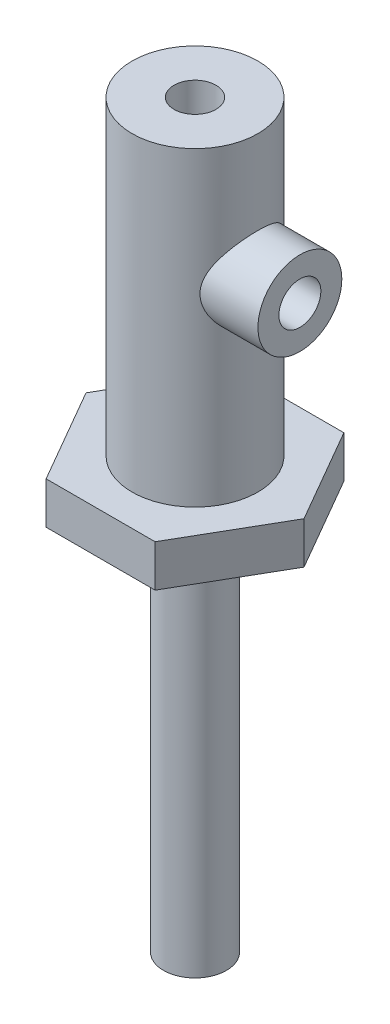
SolidWorks part; units mm, degrees
ref_plane "Front Plane" through (0, 0, 0) normal (0, 0, 1) x (1, 0, 0)
ref_plane "Top Plane" through (0, 0, 0) normal (0, 1, 0) x (1, 0, 0)
ref_plane "Right Plane" through (0, 0, 0) normal (1, 0, 0) x (0, 0, -1)
sketch "Sketch1" plane through (0, 0, 0) normal (0, 1, 0) x (1, 0, 0)
  circle A0 centre (0, 0) radius 3
  dimension "D1" = 6
extrude "Boss-Extrude1" add sketch "Sketch1" along normal blind 16.8
ref_plane "Plane1" through (0, 16.8, 0) normal (0, 1, 0) x (1, 0, 0)
ref_point "Point1"
sketch "Sketch2" plane through (0, 16.8, 0) normal (0, 1, 0) x (1, 0, 0)
  circle A0 centre (0, 0) radius 1
  dimension "D1" = 2
extrude "Cut-Extrude3" cut sketch "Sketch2" against normal blind 10.2
ref_plane "Plane2" through (0, 0, 0) normal (0, -1, 0) x (-1, 0, 0)
sketch "Sketch3" plane through (0, 0, 0) normal (0, -1, 0) x (-1, 0, 0)
  line L1 (5.1962, 0) -> (2.5981, 4.5)
  line L2 (2.5981, 4.5) -> (-2.5981, 4.5)
  line L3 (-2.5981, 4.5) -> (-5.1962, 0)
  line L4 (-5.1962, 0) -> (-2.5981, -4.5)
  line L5 (-2.5981, -4.5) -> (2.5981, -4.5)
  line L6 (2.5981, -4.5) -> (5.1962, 0)
  circle A0 centre (0, 0) radius 4.5 construction
extrude "Boss-Extrude2" add sketch "Sketch3" against normal blind 2
sketch "Sketch4" plane through (0, 0, 0) normal (0, -1, 0) x (-1, 0, 0)
  circle A0 centre (0, 0) radius 1.5
  dimension "D1" = 3
extrude "Boss-Extrude3" add sketch "Sketch4" along normal blind 18.5
ref_plane "Plane3" through (3, 0, 0) normal (1, 0, 0) x (0, 0, -1)
sketch "Sketch6" plane through (3, 0, 0) normal (1, 0, 0) x (0, 0, -1)
  line L0 (3.3, 16.8) -> (-3.3, 16.8) construction
  circle A0 centre (0, 10.8) radius 1
  circle A1 centre (0, 10.8) radius 2
  dimension "D2" = 2
  dimension "D3" = 4
  dimension "D1" = 6
extrude "Boss-Extrude4" add sketch "Sketch6" along normal blind 2 and the other way blind 1
ref_point "Point3"
sketch "Sketch7" plane through (3, 0, 0) normal (1, 0, 0) x (0, 0, -1)
  circle A0 centre (0, 10.8) radius 1.1
extrude "Cut-Extrude4" cut sketch "Sketch7" against normal blind 3
